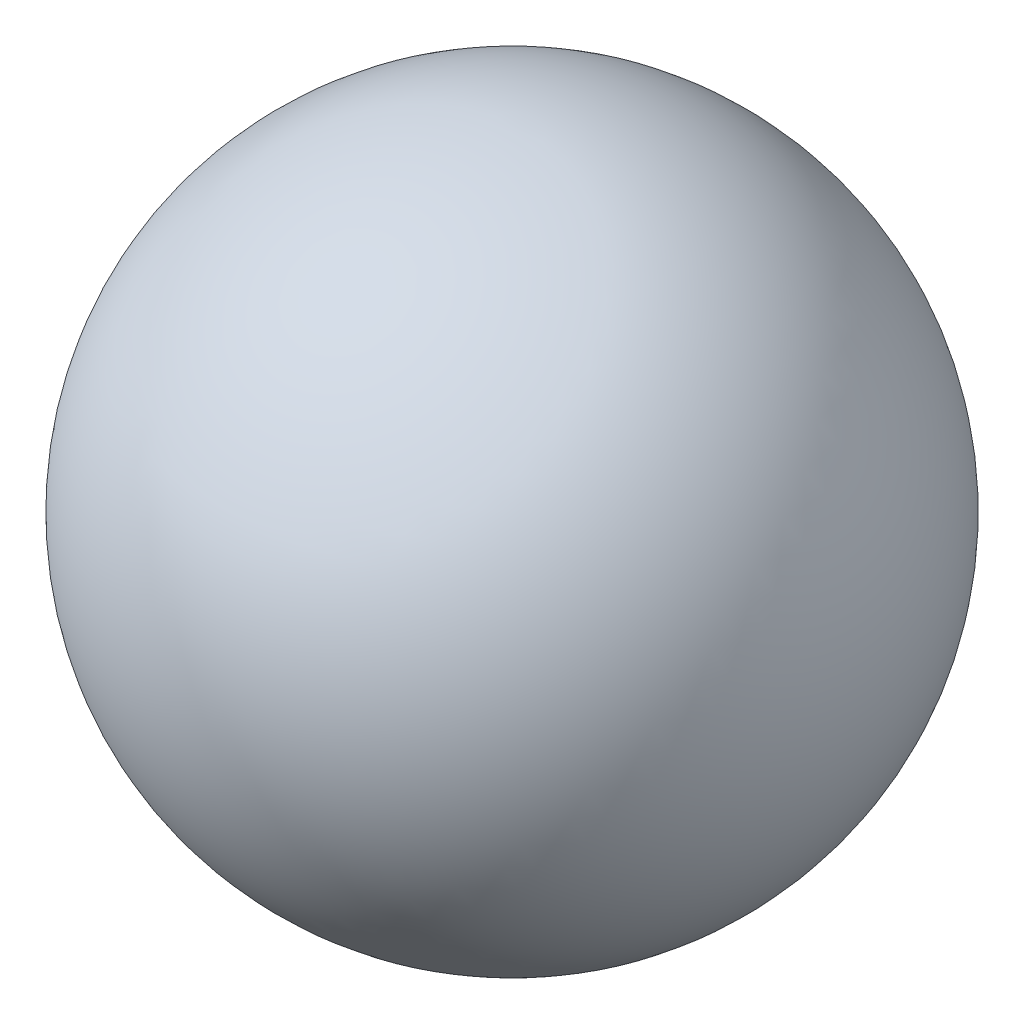
SolidWorks part; units mm, degrees
ref_plane "Front" through (0, 0, 0) normal (0, 0, 1) x (1, 0, 0)
ref_plane "Top" through (0, 0, 0) normal (0, 1, 0) x (1, 0, 0)
ref_plane "Right" through (0, 0, 0) normal (1, 0, 0) x (0, 0, -1)
sketch "Sketch2" plane through (0, 0, 0) normal (1, 0, 0) x (0, 0, -1)
  line L0 (0, -2.25) -> (0, 2.25)
  circle A0 centre (0, 0) radius 2.25 construction
  arc A1 (0, 2.25) -> (0, -2.25) centre (0, 0) cw
  dimension "D1" = 4.5
revolve "Revolve1" add sketch "Sketch2" angle 360 about L0 region at (0, 0, -0.9549)
sketch "Bearing Slot Cut Guide Loose" plane through (0, 0, 0) normal (1, 0, 0) x (0, 0, -1)
  line L0 (-1.35, 2.25) -> (1.35, 2.25)
  line L1 (1.35, 2.25) -> (1.7642, 1.8358)
  line L2 (2.35, 0.4216) -> (2.35, -0.4216)
  line L3 (-1.35, 2.25) -> (-1.7642, 1.8358)
  line L4 (-2.35, 0.4216) -> (-2.35, -0.4216)
  line L5 (0, 0) -> (0, 2.25) construction
  line L6 (0, 0) -> (-2.35, 0) construction
  line L7 (-1.35, -2.25) -> (-1.7642, -1.8358)
  line L8 (-1.35, -2.25) -> (1.35, -2.25)
  line L9 (1.35, -2.25) -> (1.7642, -1.8358)
  arc A0 (1.7642, -1.8358) -> (2.35, -0.4216) centre (0.35, -0.4216) ccw
  arc A1 (-1.7642, -1.8358) -> (-2.35, -0.4216) centre (-0.35, -0.4216) cw
  arc A2 (1.7642, 1.8358) -> (2.35, 0.4216) centre (0.35, 0.4216) cw
  circle A3 centre (0, 0) radius 2.35 construction
  arc A4 (-1.7642, 1.8358) -> (-2.35, 0.4216) centre (-0.35, 0.4216) ccw
  circle A5 centre (0, 0) radius 2.25 construction
  circle A6 centre (0, 0) radius 2.25 construction
  circle A7 centre (0, 0) radius 2.25
  point P5 (0, 2.35)
  point P14 (2.35, 0)
  point P17 (2.35, -1.25)
  point P20 (-2.35, -1.25)
  point P23 (2.35, 1.25)
  point P26 (-2.35, 1.25)
  dimension "D1" = 4.7
  dimension "D5" = 2
  dimension "D2" = 45
  dimension "D3" = 1
  dimension "D4" = 0
sketch "Bearing Slot Cut Guide Tight" plane through (0, 0, 0) normal (1, 0, 0) x (0, 0, -1)
  line L0 (-1.35, 2.25) -> (1.35, 2.25) construction
  line L1 (1.35, 2.25) -> (1.7642, 1.8358) construction
  line L2 (2.35, 0.4216) -> (2.35, -0.4216) construction
  line L3 (1.35, -2.25) -> (1.7642, -1.8358) construction
  line L4 (-1.35, -2.25) -> (1.35, -2.25) construction
  line L5 (-1.35, -2.25) -> (-1.7642, -1.8358) construction
  line L6 (-2.35, 0.4216) -> (-2.35, -0.4216) construction
  line L7 (-1.35, 2.25) -> (-1.7642, 1.8358) construction
  line L8 (-1.35, 2.25) -> (1.35, 2.25) construction
  line L9 (1.35, 2.25) -> (1.7642, 1.8358) construction
  line L10 (2.35, 0.4216) -> (2.35, -0.4216)
  line L11 (1.35, -2.25) -> (1.7642, -1.8358)
  line L12 (-1.35, -2.25) -> (1.35, -2.25)
  line L13 (-1.35, -2.25) -> (-1.7642, -1.8358)
  line L14 (-2.35, 0.4216) -> (-2.35, -0.4216)
  line L15 (-1.35, 2.25) -> (-1.7642, 1.8358) construction
  line L16 (-1.7642, 1.8358) -> (-1.375, 2.225)
  line L17 (-1.375, 2.225) -> (1.375, 2.225)
  line L18 (1.375, 2.225) -> (1.7642, 1.8358)
  arc A0 (2.35, 0.4216) -> (1.7642, 1.8358) centre (0.35, 0.4216) ccw construction
  arc A1 (1.7642, -1.8358) -> (2.35, -0.4216) centre (0.35, -0.4216) ccw construction
  arc A2 (-2.35, -0.4216) -> (-1.7642, -1.8358) centre (-0.35, -0.4216) ccw construction
  arc A3 (-1.7642, 1.8358) -> (-2.35, 0.4216) centre (-0.35, 0.4216) ccw construction
  arc A4 (2.35, 0.4216) -> (1.7642, 1.8358) centre (0.35, 0.4216) ccw
  arc A5 (1.7642, -1.8358) -> (2.35, -0.4216) centre (0.35, -0.4216) ccw
  arc A6 (-2.35, -0.4216) -> (-1.7642, -1.8358) centre (-0.35, -0.4216) ccw
  arc A7 (-1.7642, 1.8358) -> (-2.35, 0.4216) centre (-0.35, 0.4216) ccw
  dimension "D1" = 0.05
